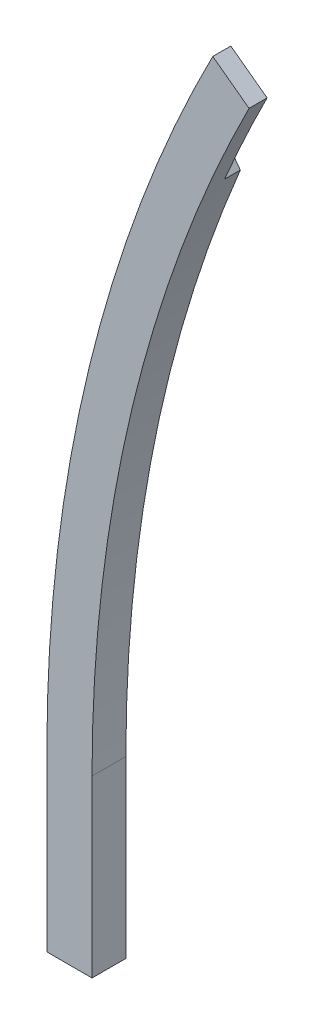
SolidWorks part; units mm, degrees
ref_plane "Front Plane" through (0, 0, 0) normal (0, 0, 1) x (1, 0, 0)
ref_plane "Top Plane" through (0, 0, 0) normal (0, 1, 0) x (1, 0, 0)
ref_plane "Right Plane" through (0, 0, 0) normal (1, 0, 0) x (0, 0, -1)
sketch "Sketch1" plane through (0, 0, 0) normal (0, 0, 1) x (1, 0, 0)
  line L0 (0, 0) -> (-12.7, 0)
  line L1 (-12.7, 0) -> (-12.7, 49.2125)
  line L5 (-12.7, 47.244) -> (-12.7, -82.4033) construction
  line L6 (0, 0) -> (0, 49.2125)
  line L8 (44.1825, 233.9977) -> (33.9621, 241.5365)
  line L9 (-16.256, 49.2125) -> (-42.799, 49.2125) construction
  line L13 (64.6325, 218.9133) -> (9.594, 259.511) construction
  arc A1 (33.9621, 241.5365) -> (-12.7, 49.2125) centre (406.9754, 49.2125) ccw
  arc A2 (44.1825, 233.9977) -> (0, 49.2125) centre (408.5064, 49.2125) ccw
  point P7 (0, 0)
  point P8 (0, 52.3912)
  point P9 (21.2842, 222.9187)
  point P13 (27.8713, 235.6428)
  point P14 (39.1409, 223.9164)
  point P15 (29.2993, 209.2905)
  point P20 (28.3044, 228.6343)
  point P22 (-12.7, 0)
  dimension "D1" = 419.6754
extrude "Boss-Extrude1" add sketch "Sketch1" along normal blind 9.525
sketch "Sketch3" plane through (0, 0, 0) normal (0, 0, -1) x (-1, 0, 0)
  line L0 (-33.9621, 241.5365) -> (-44.1825, 233.9977)
  line L2 (-23.5583, 219.8548) -> (-32.2084, 208.201)
  line L3 (-0.7257, 250.6161) -> (-57.873, 173.6244) construction
  arc A0 (-44.1825, 233.9977) -> (-32.2084, 208.201) centre (-408.5064, 49.2125) cw
  arc A2 (-33.9621, 241.5365) -> (-23.5583, 219.8548) centre (-406.9754, 49.2125) cw
  arc A3 (12.7, 49.2125) -> (-33.9621, 241.5365) centre (-406.9754, 49.2125) ccw construction
  arc A4 (0, 49.2125) -> (-44.1825, 233.9977) centre (-408.5064, 49.2125) ccw construction
  point P5 (-17.8221, 206.334)
  point P14 (-32.1975, 208.175)
extrude "Cut-Extrude5" cut sketch "Sketch3" against normal blind 4.445
